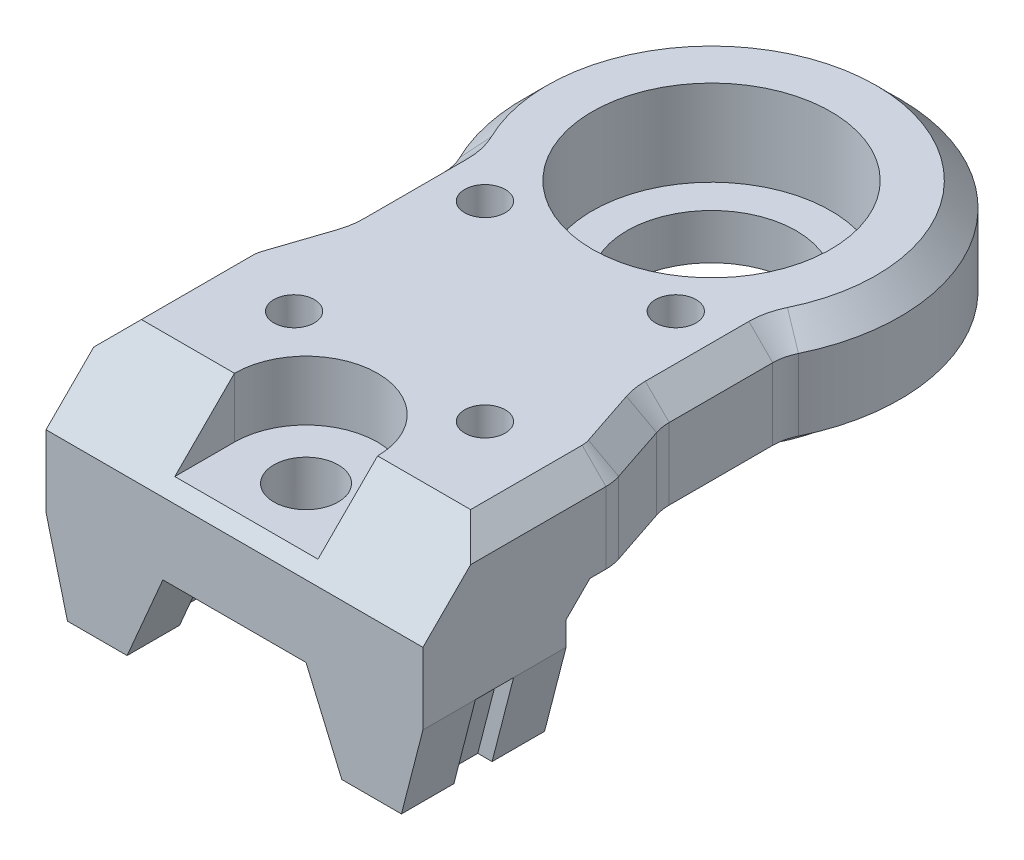
SolidWorks part; units mm, degrees
material "ABS"
ref_plane "正面" through (0, 0, 0) normal (0, 0, 1) x (1, 0, 0)
ref_plane "平面" through (0, 0, 0) normal (0, 1, 0) x (1, 0, 0)
ref_plane "右側面" through (0, 0, 0) normal (1, 0, 0) x (0, 0, -1)
sketch "ｽｹｯﾁ1" plane through (0, 0, 0) normal (0, 1, 0) x (1, 0, 0)
  line L2 (-7.9, 0) -> (-7.9, -20)
  line L3 (-7.9, -20) -> (7.9, -20)
  line L4 (7.9, 0) -> (7.9, -20)
  line L5 (-7.9, 0) -> (7.9, -20) construction
  line L6 (-7.9, -20) -> (7.9, 0) construction
  arc A0 (7.9, 0) -> (-7.9, 0) centre (0, 0) ccw
  point P7 (0, -10)
  dimension "D2" = 0
  dimension "D4" = 20
  dimension "D3" = 15.8
extrude "ﾎﾞｽ - 押し出し1" add sketch "ｽｹｯﾁ1" along normal blind 4
sketch "ｽｹｯﾁ4" plane through (0, 0, 20) normal (0, 0, 1) x (1, 0, 0)
  line L1 (-7, -5.5) -> (-4.5, -5.5)
  line L2 (-4.5, -5.5) -> (-3, -2)
  line L3 (-3, -2) -> (3, -2)
  line L4 (3, -2) -> (4.5, -5.5)
  line L5 (4.5, -5.5) -> (7, -5.5)
  line L7 (7.9, 0) -> (-7.9, 0)
  line L8 (-7, -5.5) -> (-7.9, -2)
  line L9 (-7.9, -2) -> (-7.9, 0)
  line L10 (7.9, 0) -> (7.9, -2)
  line L11 (7.9, -2) -> (7, -5.5)
  dimension "D1" = 5.5
  dimension "D2" = 3.5
  dimension "D3" = 7
  dimension "D4" = 3
  dimension "D5" = 2.5
  dimension "D9" = 2
  dimension "D10" = 2
extrude "ﾎﾞｽ - 押し出し3" add sketch "ｽｹｯﾁ4" against normal blind 6
chamfer "面取り1" distance 3 angle 45 1 edges at (0, 4, 20)
sketch "ｽｹｯﾁ5" plane through (0, 4, 0) normal (0, 1, 0) x (1, 0, 0)
  line L0 (-4, -13.5) -> (4, -13.5) construction
  line L1 (7.9, -20) -> (-7.9, -20) construction
  circle A0 centre (-4, -13.5) radius 0.85
  circle A1 centre (4, -13.5) radius 0.85
  dimension "D1" = 1.7
  dimension "D2" = 1.7
  dimension "D4" = 4
  dimension "D3" = 8
  dimension "D5" = 6.5
extrude "ｶｯﾄ - 押し出し1" cut sketch "ｽｹｯﾁ5" against normal blind 4
sketch "ｽｹｯﾁ6" plane through (0, 4, 0) normal (0, 1, 0) x (1, 0, 0)
  line L0 (-3, -17) -> (-3, -21)
  line L1 (-3, -21) -> (3, -21)
  line L2 (3, -21) -> (3, -17)
  line L3 (7.9, -20) -> (-7.9, -20) construction
  arc A0 (3, -17) -> (-3, -17) centre (0, -17) ccw
  dimension "D1" = 6
  dimension "D3" = 3
  dimension "D2" = 0
  dimension "D4" = 4
extrude "ｶｯﾄ - 押し出し2" cut sketch "ｽｹｯﾁ6" against normal blind 2.5
sketch "ｽｹｯﾁ7" plane through (0, 1.5, 0) normal (0, 1, 0) x (1, 0, 0)
  circle A0 centre (0, -17) radius 1.35
  dimension "D1" = 2.7
extrude "ｶｯﾄ - 押し出し3" cut sketch "ｽｹｯﾁ7" against normal up to next
sketch "ｽｹｯﾁ8" plane through (0, 0, 0) normal (0, -1, 0) x (1, 0, 0)
  circle A0 centre (0, 0) radius 6
  dimension "D1" = 12
extrude "ﾎﾞｽ - 押し出し4" add sketch "ｽｹｯﾁ8" along normal blind 1.5
sketch "ｽｹｯﾁ9" plane through (0, 4, 0) normal (0, 1, 0) x (1, 0, 0)
  circle A0 centre (0, 0) radius 5
  dimension "D1" = 10
extrude "ｶｯﾄ - 押し出し4" cut sketch "ｽｹｯﾁ9" against normal blind 3.6
sketch "ｽｹｯﾁ10" plane through (0, 0.4, 0) normal (0, 1, 0) x (1, 0, 0)
  circle A0 centre (0, 0) radius 3.55
  dimension "D1" = 7.1
extrude "ｶｯﾄ - 押し出し5" cut sketch "ｽｹｯﾁ10" against normal blind 3.6
ref_plane "平面1" through (0, 0, 17) normal (0, 0, 1) x (1, 0, 0)
sketch "ｽｹｯﾁ11" plane through (0, 0, 17) normal (0, 0, 1) x (1, 0, 0)
  line L0 (3, -2) -> (4.5, -5.5)
  line L1 (3, -2) -> (3.6, -2)
  line L2 (4.5, -5.5) -> (5.1, -5.5)
  line L3 (3.6, -2) -> (5.1, -5.5)
  line L4 (3, -2) -> (5.1, -5.5) construction
  line L5 (4.5, -5.5) -> (3.6, -2) construction
  line L6 (4.5, -5.5) -> (7, -5.5) construction
  line L7 (7, -5.5) -> (6.4, -5.5)
  line L8 (7, -5.5) -> (7.9, -2)
  line L9 (6.4, -5.5) -> (7.3, -2)
  line L10 (7.9, -2) -> (7.3, -2)
  line L11 (7, -5.5) -> (7.3, -2) construction
  line L12 (6.4, -5.5) -> (7.9, -2) construction
  point P5 (4.05, -3.75)
  point P14 (7.15, -3.75)
  dimension "D1" = 0.6
extrude "ｶｯﾄ - 押し出し6" cut sketch "ｽｹｯﾁ11" against normal mid plane 1.6
mirror "ﾐﾗｰ1" about plane through (0, 0, 0) normal (1, 0, 0) of "ｶｯﾄ - 押し出し6"
pattern_linear "直線ﾊﾟﾀｰﾝ1" count 2 spacing 8 along (0, 0, -1) of "ｶｯﾄ - 押し出し1"
sketch "ｽｹｯﾁ12" plane through (0, 4, 0) normal (0, 1, 0) x (1, 0, 0)
  line L0 (-7.9, 0) -> (-7.9, -12)
  line L1 (-7.9, 0) -> (-7.9, -17) construction
  line L2 (-7.9, -12) -> (-6.9, -9)
  line L3 (-6.9, -9) -> (-6.9, -3.8471)
  line L4 (7.9, -20) -> (-7.9, -20) construction
  arc A0 (-7.9, 0) -> (-6.9, -3.8471) centre (0, 0) ccw
  arc A1 (7.9, 0) -> (-7.9, 0) centre (0, 0) ccw construction
  dimension "D1" = 6.9
  dimension "D2" = 3
  dimension "D3" = 11
extrude "ｶｯﾄ - 押し出し7" cut sketch "ｽｹｯﾁ12" against normal through all
mirror "ﾐﾗｰ2" about plane through (0, 0, 0) normal (1, 0, 0) of "ｶｯﾄ - 押し出し7"
fillet "ﾌｨﾚｯﾄ1" radius 2 6 edges at (6.9, 2, 3.8471) (7.9, 2, 12) (6.9, 2, 9) (-7.9, 2, 12) (-6.9, 2, 9) (-6.9, 2, 3.8471)
chamfer "面取り2" distance 1 angle 45 16 edges at (6.2937, 0, 14) (0, 0, 14) (-6.2937, 0, 14) (7.9, 4, 14.6623) (7.8742, 4, 12.0042) (7.4, 4, 10.5) (6.9258, 4, 8.9958) (-7.9, 4, 14.6623) (6.9, 4, 6.5057) (-7.8742, 4, 12.0042) (6.9512, 4, 3.8864) (-7.4, 4, 10.5) (0, 4, -7.9) (-6.9258, 4, 8.9958) (-6.9512, 4, 3.8864) (-6.9, 4, 6.5057)
